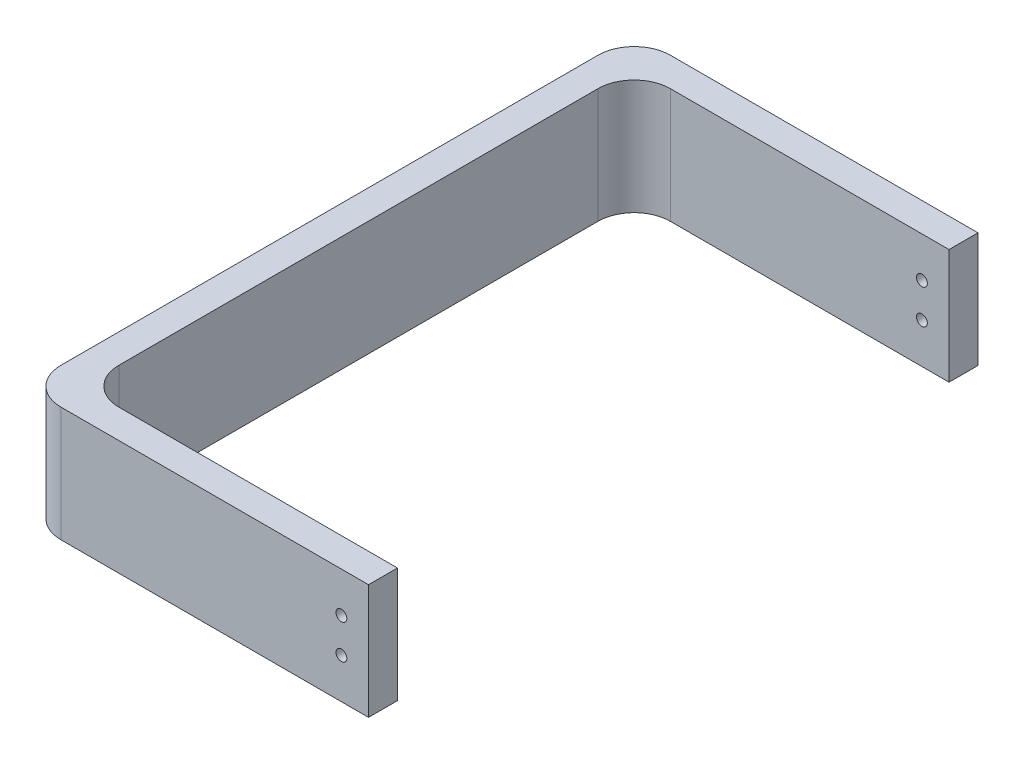
SolidWorks part; units mm, degrees
material "TPU"
ref_plane "Front Plane" through (0, 0, 0) normal (0, 0, 1) x (1, 0, 0)
ref_plane "Top Plane" through (0, 0, 0) normal (0, 1, 0) x (1, 0, 0)
ref_plane "Right Plane" through (0, 0, 0) normal (1, 0, 0) x (0, 0, -1)
sketch "Sketch1" plane through (0, 0, 0) normal (0, 1, 0) x (1, 0, 0)
  line L0 (0, 0) -> (-95, 0)
  line L1 (-95, 0) -> (-95, 168.4)
  line L2 (-95, 168.4) -> (0, 168.4)
  line L3 (0, 8) -> (-87, 8)
  line L4 (-87, 8) -> (-87, 160.4)
  line L5 (-87, 160.4) -> (0, 160.4)
  line L6 (0, 168.4) -> (0, 160.4)
  line L7 (0, 8) -> (0, 0)
  dimension "D1" = 95
  dimension "D2" = 152.4
  dimension "D3" = 0
  dimension "D4" = 8
extrude "Boss-Extrude1" add sketch "Sketch1" along normal blind 31.75
sketch "Sketch2" plane through (0, 0, 0) normal (0, 0, 1) x (1, 0, 0)
  line L2 (-95, 31.75) -> (0, 31.75) construction
  line L3 (-95, 0) -> (0, 0) construction
  line L4 (0, 31.75) -> (0, 0) construction
  circle A0 centre (-7.5, 20.6375) radius 1.5
  circle A1 centre (-7.5, 11.1125) radius 1.5
  point P0 (-7.5, 20.6375)
  point P1 (-7.5, 11.1125)
  dimension "D5" = 3
  dimension "D6" = 3
  dimension "D1" = 9.525
  dimension "D2" = 11.1125
  dimension "D3" = 11.1125
  dimension "D4" = 7.5
extrude "Cut-Extrude1" cut sketch "Sketch2" against normal through all contours A1 | A0 region at (-7.5, 11.1125, 0)
fillet "Fillet1" radius 10 4 edges at (-95, 15.875, -168.4) (-87, 15.875, -160.4) (-87, 15.875, -8) (-95, 15.875, 0)
